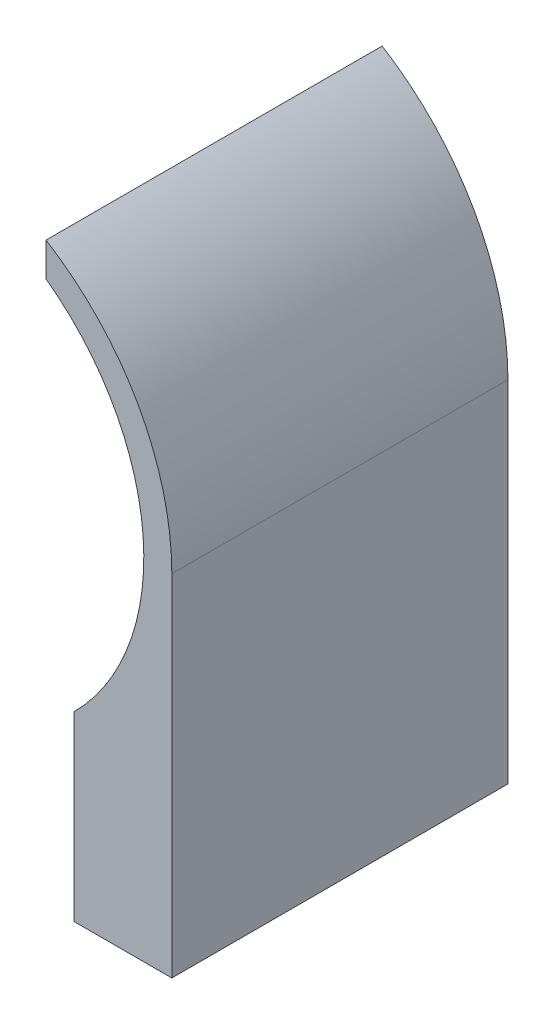
SolidWorks part; units mm, degrees
material "201 Annealed Stainless Steel (SS)"
ref_plane "Front Plane" through (0, 0, 0) normal (0, 0, 1) x (1, 0, 0)
ref_plane "Top Plane" through (0, 0, 0) normal (0, 1, 0) x (1, 0, 0)
ref_plane "Right Plane" through (0, 0, 0) normal (1, 0, 0) x (0, 0, -1)
sketch "Sketch2" plane through (0, 0, 0) normal (0, 0, 1) x (1, 0, 0)
  line L0 (-81.7487, 0) -> (129.7647, 0) construction
  line L1 (0, 82.2046) -> (0, -95) construction
  line L2 (50.1, 0) -> (50.1, 106.5165) construction
  line L3 (60, -60.208) -> (60, -125)
  line L5 (95, 0) -> (95, -125)
  line L6 (95, -125) -> (60, -125)
  line L7 (50.1, 80.7155) -> (50.1, 68.6658)
  line L8 (0, -95) -> (0, -125) construction
  line L9 (0, -125) -> (111.0903, -125) construction
  line L10 (-60, -60.208) -> (60, -60.208) construction
  circle A0 centre (0, 0) radius 85 construction
  circle A1 centre (0, 0) radius 95 construction
  arc A2 (50.1, 68.6658) -> (60, -60.208) centre (0, 0) cw
  arc A3 (95, 0) -> (50.1, 80.7155) centre (0, 0) ccw
  point P10 (0, 0)
  dimension "D1" = 170
  dimension "D2" = 190
  dimension "D5" = 30
  dimension "D3" = 50.1
  dimension "D6" = 120
extrude "Inner Ring - Right Side" add sketch "Sketch2" along normal blind 120
